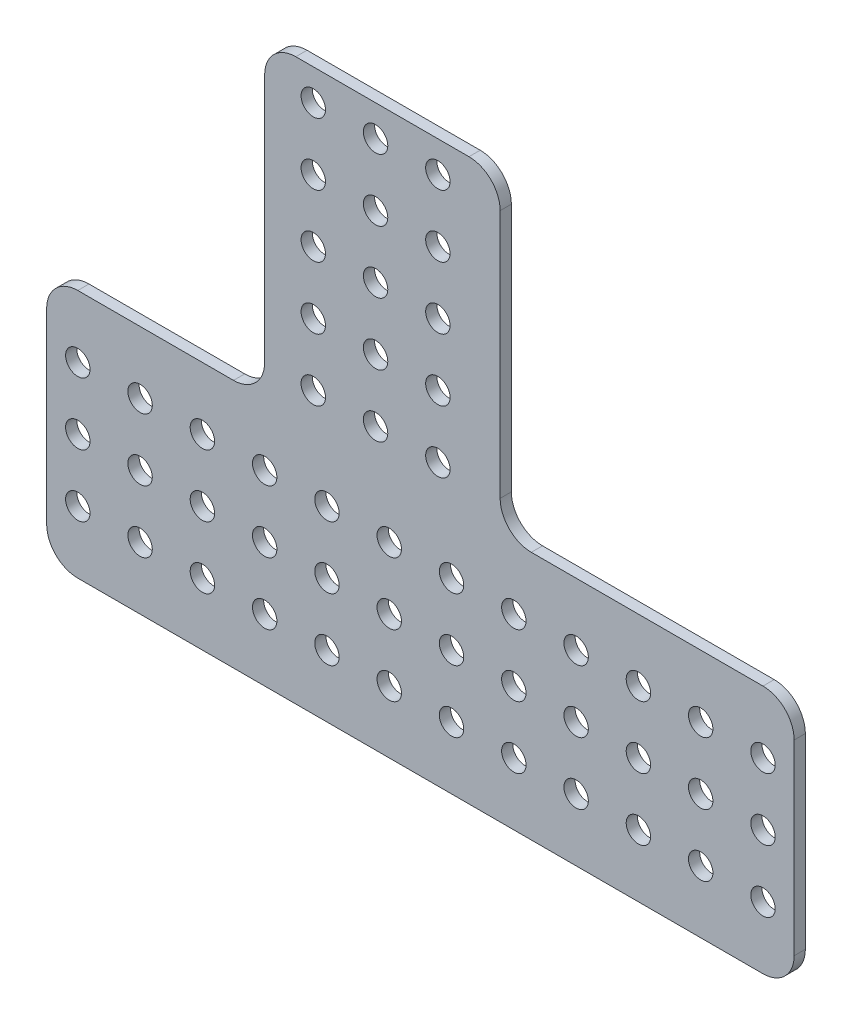
SolidWorks part; units mm, degrees
ref_plane "Front Plane" through (0, 0, 0) normal (0, 0, 1) x (1, 0, 0)
ref_plane "Top Plane" through (0, 0, 0) normal (0, 1, 0) x (1, 0, 0)
ref_plane "Right Plane" through (0, 0, 0) normal (1, 0, 0) x (0, 0, -1)
sketch "Sketch1" plane through (0, 0, 0) normal (0, 0, 1) x (1, 0, 0)
  line L0 (-255.429, 188.8429) -> (-220.1184, 188.8429)
  line L1 (-213.7684, 182.4929) -> (-213.7684, 131.6929)
  line L2 (-207.4184, 125.3429) -> (-160.179, 125.3429)
  line L3 (-153.829, 118.9929) -> (-153.829, 80.8929)
  line L4 (-160.179, 74.5429) -> (-299.879, 74.5429)
  line L5 (-306.229, 80.8929) -> (-306.229, 118.9929)
  line L6 (-299.879, 125.3429) -> (-268.129, 125.3429)
  line L7 (-261.779, 131.6929) -> (-261.779, 182.4929)
  line L8 (-264.5684, 125.3429) -> (-213.7684, 125.3429) construction
  line L9 (-213.7684, 811.1429) -> (-213.7684, 125.3429) construction
  line L10 (-299.879, 112.6429) -> (-287.179, 112.6429) construction
  line L11 (-299.879, 112.6429) -> (-299.879, 99.9429) construction
  arc A0 (-268.129, 125.3429) -> (-261.779, 131.6929) centre (-268.129, 131.6929) ccw
  arc A1 (-306.229, 118.9929) -> (-299.879, 125.3429) centre (-299.879, 118.9929) cw
  arc A2 (-299.879, 74.5429) -> (-306.229, 80.8929) centre (-299.879, 80.8929) cw
  arc A3 (-153.829, 80.8929) -> (-160.179, 74.5429) centre (-160.179, 80.8929) cw
  arc A4 (-160.179, 125.3429) -> (-153.829, 118.9929) centre (-160.179, 118.9929) cw
  arc A5 (-213.7684, 131.6929) -> (-207.4184, 125.3429) centre (-207.4184, 131.6929) ccw
  arc A6 (-255.429, 188.8429) -> (-261.779, 182.4929) centre (-255.429, 182.4929) ccw
  arc A7 (-220.1184, 188.8429) -> (-213.7684, 182.4929) centre (-220.1184, 182.4929) cw
  circle A8 centre (-226.4684, 182.4929) radius 2.4892 construction
  circle A9 centre (-226.4684, 157.0929) radius 2.4892 construction
  circle A10 centre (-226.4684, 144.3929) radius 2.4892 construction
  circle A11 centre (-226.4684, 131.6929) radius 2.4892 construction
  circle A12 centre (-239.1684, 131.6929) radius 2.4892 construction
  circle A13 centre (-251.8684, 131.6929) radius 2.4892 construction
  circle A14 centre (-251.8684, 144.3929) radius 2.4892 construction
  circle A15 centre (-239.1684, 144.3929) radius 2.4892 construction
  circle A16 centre (-239.1684, 157.0929) radius 2.4892 construction
  circle A17 centre (-251.8684, 157.0929) radius 2.4892 construction
  circle A18 centre (-226.4684, 169.7929) radius 2.4892 construction
  circle A19 centre (-239.1684, 182.4929) radius 2.4892 construction
  circle A20 centre (-239.1684, 169.7929) radius 2.4892 construction
  circle A21 centre (-251.8684, 169.7929) radius 2.4892 construction
  circle A22 centre (-251.8684, 182.4929) radius 2.4892 construction
  circle A23 centre (-226.4684, 157.0929) radius 2.4892
  circle A24 centre (-226.4684, 144.3929) radius 2.4892
  circle A25 centre (-226.4684, 131.6929) radius 2.4892
  circle A26 centre (-239.1684, 131.6929) radius 2.4892
  circle A27 centre (-251.8684, 131.6929) radius 2.4892
  circle A28 centre (-251.8684, 144.3929) radius 2.4892
  circle A29 centre (-239.1684, 144.3929) radius 2.4892
  circle A30 centre (-239.1684, 157.0929) radius 2.4892
  circle A31 centre (-251.8684, 157.0929) radius 2.4892
  circle A32 centre (-226.4684, 169.7929) radius 2.4892
  circle A33 centre (-226.4684, 182.4929) radius 2.4892
  circle A34 centre (-239.1684, 182.4929) radius 2.4892
  circle A35 centre (-239.1684, 169.7929) radius 2.4892
  circle A36 centre (-251.8684, 169.7929) radius 2.4892
  circle A37 centre (-251.8684, 182.4929) radius 2.4892
  circle A38 centre (-299.879, 112.6429) radius 2.4892
  circle A39 centre (-287.179, 112.6429) radius 2.4892
  circle A40 centre (-274.479, 112.6429) radius 2.4892
  circle A41 centre (-261.779, 112.6429) radius 2.4892
  circle A42 centre (-249.079, 112.6429) radius 2.4892
  circle A43 centre (-236.379, 112.6429) radius 2.4892
  circle A44 centre (-223.679, 112.6429) radius 2.4892
  circle A45 centre (-210.979, 112.6429) radius 2.4892
  circle A46 centre (-198.279, 112.6429) radius 2.4892
  circle A47 centre (-185.579, 112.6429) radius 2.4892
  circle A48 centre (-172.879, 112.6429) radius 2.4892
  circle A49 centre (-160.179, 112.6429) radius 2.4892
  circle A50 centre (-287.179, 99.9429) radius 2.4892
  circle A51 centre (-274.479, 99.9429) radius 2.4892
  circle A52 centre (-261.779, 99.9429) radius 2.4892
  circle A53 centre (-249.079, 99.9429) radius 2.4892
  circle A54 centre (-236.379, 99.9429) radius 2.4892
  circle A55 centre (-223.679, 99.9429) radius 2.4892
  circle A56 centre (-210.979, 99.9429) radius 2.4892
  circle A57 centre (-198.279, 99.9429) radius 2.4892
  circle A58 centre (-185.579, 99.9429) radius 2.4892
  circle A59 centre (-172.879, 99.9429) radius 2.4892
  circle A60 centre (-160.179, 99.9429) radius 2.4892
  circle A61 centre (-287.179, 87.2429) radius 2.4892
  circle A62 centre (-274.479, 87.2429) radius 2.4892
  circle A63 centre (-261.779, 87.2429) radius 2.4892
  circle A64 centre (-249.079, 87.2429) radius 2.4892
  circle A65 centre (-236.379, 87.2429) radius 2.4892
  circle A66 centre (-223.679, 87.2429) radius 2.4892
  circle A67 centre (-210.979, 87.2429) radius 2.4892
  circle A68 centre (-198.279, 87.2429) radius 2.4892
  circle A69 centre (-185.579, 87.2429) radius 2.4892
  circle A70 centre (-172.879, 87.2429) radius 2.4892
  circle A71 centre (-160.179, 87.2429) radius 2.4892
  circle A72 centre (-299.879, 99.9429) radius 2.4892
  circle A73 centre (-299.879, 87.2429) radius 2.4892
  dimension "D2" = 6.35
  dimension "D6" = 12.7
  dimension "D8" = 4.9784
  dimension "D9" = 12
  dimension "D4" = 6.35
  dimension "D1" = 6.35
  dimension "D3" = 152.4
  dimension "D5" = 50.8
  dimension "D7" = 44.45
  dimension "D11" = 12.7
  dimension "D12" = 12.7
  dimension "D10" = 3
extrude "Boss-Extrude1" add sketch "Sketch1" along normal blind 2.286
